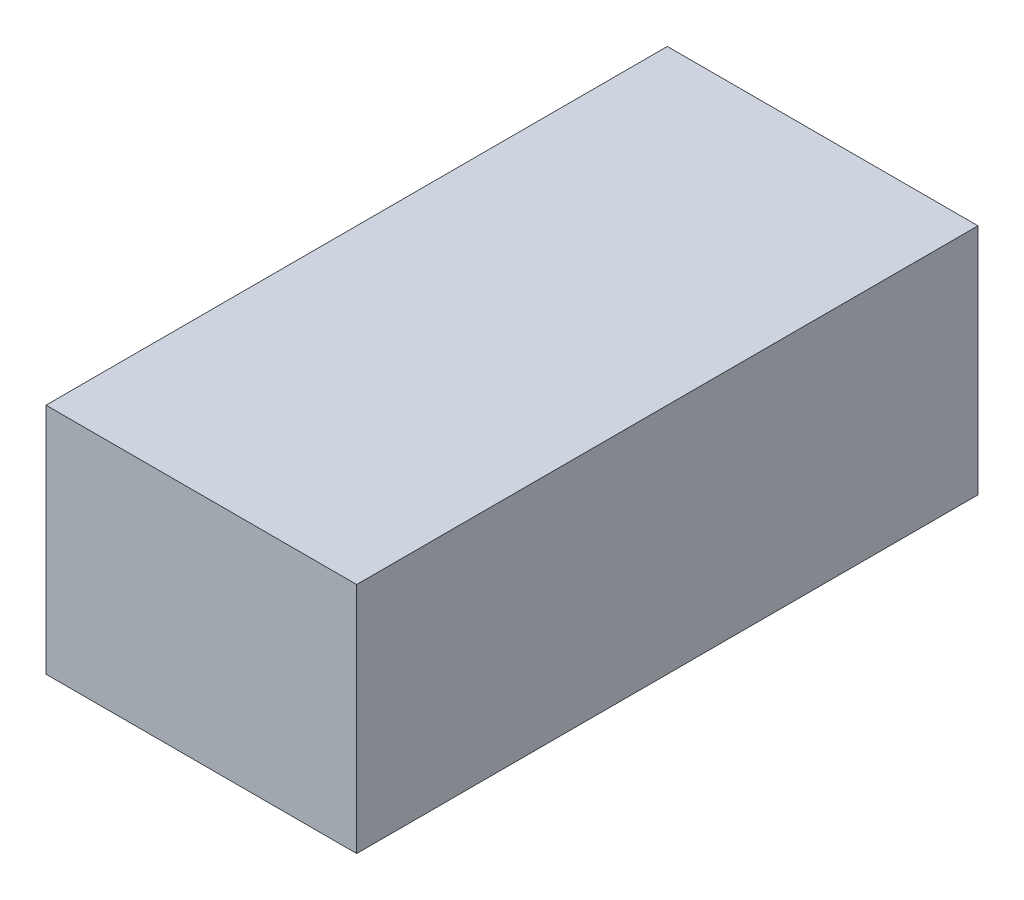
SolidWorks part; units mm, degrees
ref_plane "Ebene vorne" through (0, 0, 0) normal (0, 0, 1) x (1, 0, 0)
ref_plane "Ebene oben" through (0, 0, 0) normal (0, 1, 0) x (1, 0, 0)
ref_plane "Ebene rechts" through (0, 0, 0) normal (1, 0, 0) x (0, 0, -1)
sketch "Sketch1" plane through (0, 0, 0) normal (0, 1, 0) x (1, 0, 0)
  line L1 (0, 0) -> (20, 0)
  line L2 (0, 0) -> (0, 40)
  line L3 (0, 40) -> (20, 40)
  line L4 (20, 0) -> (20, 40)
  dimension "D1" = 40
  dimension "D2" = 20
extrude "Boss-Extrude1" add sketch "Sketch1" along normal blind 15
